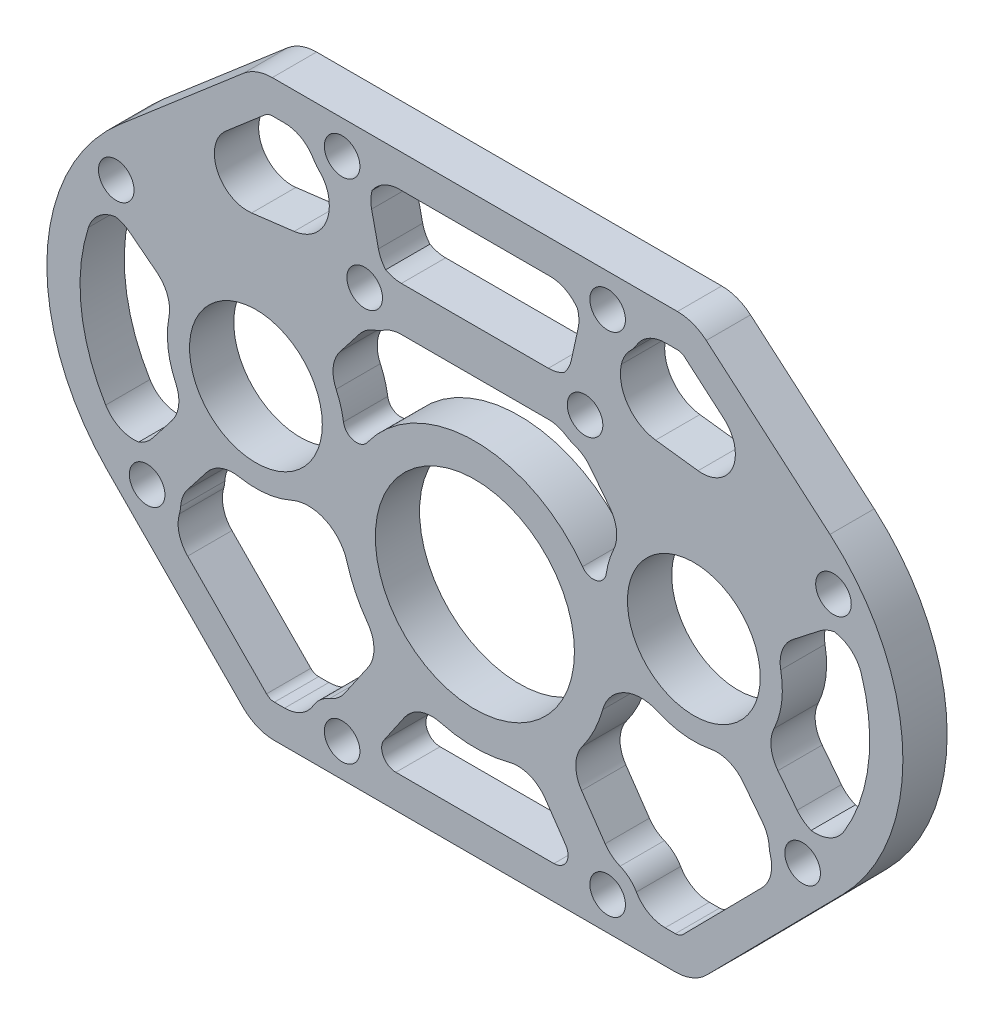
SolidWorks part; units mm, degrees
material "6061-T6 (SS)"
ref_plane "Front Plane" through (0, 0, 0) normal (0, 0, 1) x (1, 0, 0)
ref_plane "Top Plane" through (0, 0, 0) normal (0, 1, 0) x (1, 0, 0)
ref_plane "Right Plane" through (0, 0, 0) normal (1, 0, 0) x (0, 0, -1)
sketch "Sketch1" plane through (0, 0, 0) normal (0, 0, 1) x (1, 0, 0)
  line L0 (127, 25.4) -> (127, 0) construction
  line L1 (0, 0) -> (254, 0)
  line L2 (0, 0) -> (0, 25.4)
  line L3 (0, 25.4) -> (254, 25.4)
  line L4 (254, 0) -> (254, 25.4)
  line L18 (110.6338, 19.05) -> (106.9677, 12.7)
  line L19 (106.9677, 12.7) -> (110.6338, 6.35)
  line L20 (110.6338, 6.35) -> (117.9662, 6.35)
  line L21 (117.9662, 6.35) -> (121.6323, 12.7)
  line L22 (121.6323, 12.7) -> (117.9662, 19.05)
  line L23 (117.9662, 19.05) -> (110.6338, 19.05)
  circle A0 centre (82.8819, 22.86) radius 30 construction
  circle A1 centre (145.7181, 22.86) radius 30 construction
  circle A2 centre (82.8819, 22.86) radius 7.62 construction
  circle A3 centre (145.7181, 22.86) radius 8.636
  circle A4 centre (82.8819, 22.86) radius 8.636
  circle A5 centre (145.7181, 22.86) radius 7.62 construction
  circle A6 centre (114.3, 12.7) radius 25.4 construction
  circle A7 centre (114.3, 12.7) radius 26.67
  circle A8 centre (114.3, 12.7) radius 22.2377 construction
  circle A11 centre (114.3, 12.7) radius 6.35 construction
  dimension "D4" = 17.272
  dimension "D9" = 53.34
  dimension "D13" = 12.7
  dimension "D1" = 25.4
  dimension "D2" = 254
  dimension "D10" = 12.7
  dimension "D12" = 12.7
  dimension "D14" = 10.16
sketch "Sketch3" plane through (0, 0, 0) normal (0, 0, 1) x (1, 0, 0)
  line L0 (82.8819, 52.86) -> (145.7181, 52.86) construction
  line L5 (82.8819, -7.14) -> (145.7181, -7.14) construction
  line L6 (82.8819, 22.86) -> (98.4918, 42.8972) construction
  line L9 (114.3, 52.86) -> (114.3, -19.84) construction
  line L10 (63.3497, 45.6304) -> (82.8819, 62.385)
  line L25 (82.8819, 62.385) -> (145.7181, 62.385)
  line L26 (145.7181, 62.385) -> (165.2503, 45.6304)
  line L27 (110.6338, 19.05) -> (106.9677, 12.7)
  line L28 (106.9677, 12.7) -> (110.6338, 6.35)
  line L29 (110.6338, 6.35) -> (117.9662, 6.35)
  line L30 (117.9662, 6.35) -> (121.6323, 12.7)
  line L31 (121.6323, 12.7) -> (117.9662, 19.05)
  line L32 (117.9662, 19.05) -> (110.6338, 19.05)
  line L33 (110.565, 18.9308) -> (106.9677, 12.7)
  line L34 (106.9677, 12.7) -> (110.6338, 6.35)
  line L35 (110.6338, 6.35) -> (117.9662, 6.35)
  line L36 (117.9662, 6.35) -> (121.6323, 12.7)
  line L37 (121.6323, 12.7) -> (117.9662, 19.05)
  line L38 (117.9662, 19.05) -> (110.6338, 19.05)
  line L39 (96.3395, 30.6605) -> (132.2605, -5.2605) construction
  line L40 (82.8819, 22.86) -> (114.3, 12.7) construction
  line L41 (95.25, 57.6225) -> (133.35, 57.6225) construction
  line L43 (95.25, -15.0775) -> (133.35, -15.0775) construction
  line L44 (145.7181, -19.84) -> (167.0663, 1.7827)
  line L45 (82.8819, -19.84) -> (145.7181, -19.84)
  line L46 (61.5337, 1.7827) -> (82.8819, -19.84)
  line L47 (82.8819, 22.86) -> (67.272, 2.8228) construction
  line L48 (82.8819, 22.86) -> (67.272, 2.8228) construction
  line L49 (82.8819, 22.86) -> (62.8447, 38.4699) construction
  circle A2 centre (82.8819, 22.86) radius 30 construction
  circle A9 centre (114.3, 12.7) radius 26.67
  circle A10 centre (114.3, 12.7) radius 26.67 construction
  circle A11 centre (82.8819, 22.86) radius 8.636
  circle A12 centre (82.8819, 22.86) radius 8.636 construction
  circle A13 centre (145.7181, 22.86) radius 8.636
  circle A16 centre (145.7181, 22.86) radius 8.636 construction
  circle A17 centre (95.25, 57.6225) radius 2.5527
  circle A19 centre (114.3, 12.7) radius 25.4 construction
  circle A20 centre (114.3, 12.7) radius 22.2377 construction
  circle A22 centre (114.3, 12.7) radius 25.4 construction
  circle A23 centre (114.3, 12.7) radius 22.2377 construction
  arc A24 (112.6104, 26.8872) -> (104.6233, 2.1884) centre (82.8819, 22.86) ccw
  circle A25 centre (114.3, 12.7) radius 14.2875
  circle A26 centre (82.8819, 22.86) radius 9.525
  circle A27 centre (145.7181, 22.86) radius 9.525
  circle A37 centre (133.35, 57.6225) radius 2.5527
  circle A38 centre (133.35, -15.0775) radius 2.5527
  circle A39 centre (95.25, -15.0775) radius 2.5527
  circle A40 centre (67.272, 2.8228) radius 2.5527
  circle A41 centre (62.8447, 38.4699) radius 2.5527
  circle A42 centre (98.4918, 42.8972) radius 2.5527
  circle A43 centre (161.328, 2.8228) radius 2.5527
  circle A44 centre (165.7553, 38.4699) radius 2.5527
  circle A45 centre (130.1082, 42.8972) radius 2.5527
  circle A46 centre (95.25, -15.0775) radius 4.7625 construction
  arc A47 (123.9767, 2.1884) -> (115.9896, 26.8872) centre (145.7181, 22.86) ccw
  circle A48 centre (133.35, -15.0775) radius 4.7625 construction
  circle A49 centre (95.25, 57.6225) radius 4.7625 construction
  circle A50 centre (133.35, 57.6225) radius 4.7625 construction
  point P2 (114.3, 52.86)
  point P31 (114.3, -19.84)
  point P41 (114.3, 62.385)
  point P59 (114.3, 57.6225)
  point P60 (114.3, -15.0775)
  point P69 (114.3, 12.7)
  point P78 (82.8819, 22.86)
  point P84 (114.3, -22.0625)
  dimension "D3" = 70
  dimension "D4" = 9.525
  dimension "D2" = 45
  dimension "D8" = 25.4
  dimension "D14" = 28.575
  dimension "D15" = 19.05
  dimension "D16" = 3
  dimension "D5" = 5.1054
  dimension "D12" = 5.1054
  dimension "D7" = 4.7625
  dimension "D17" = 90
  dimension "2" = 50.8
  dimension "D6" = 19.05
  dimension "D18" = 7.9375
  dimension "D9" = 0
  dimension "D10" = 0
  dimension "D11" = 0
  dimension "D13" = 0
extrude "Boss-Extrude1" add sketch "Sketch3" along normal blind 6.35 contours A24 A10 L26 L25 L10 A37 A17 | A24 L46 L45 L44 A10 A38 A39 | A10 A24 A12 A40 A42 | A23 A24 A25 | A23 A22 A12 | A22 A24 A10 A12 | A22 A12 A10 A24 | A24 A22 A23 | A24 A10 A22 | A22 A24 A23 | A25 A24 A23 | A25 A23 A24 | A24 A23 A22 | A24 A22 A10 | A23 A24 A22 | A23 A45 A25 A44 | A22 A45 A23 A44 A16 | A23 A45 A22 | A22 A45 A16 A10 | A10 A16 A43 | A22 A44 A23 | A22 A44 A10 A16 | A10 A26 A12 | A22 A12 A10 | A12 A22 | A10 A27 A16 | A16 A22 | A22 A16 A10 region at (87.3231, 51.7029, 0) region at (114.3, 53.784, 0) region at (76.6658, -7.5892, 0) region at (98.4388, 17.8292, 0) region at (114.3, 34.3639, 0) region at (114.3, -6.358, 0) region at (141.2769, 51.7029, 0) region at (130.1612, 17.8292, 0)
fillet "Fillet1" radius 6.35 4 edges at (145.7181, -19.84, 3.175) (82.8819, -19.84, 3.175) (145.7181, 62.385, 3.175) (82.8819, 62.385, 3.175)
sketch "Sketch4" plane through (0, 0, 6.35) normal (0, 0, 1) x (1, 0, 0)
  line L0 (85.536, -15.0775) -> (143.064, -15.0775)
  line L1 (144.1937, -14.6053) -> (163.6773, 5.1287)
  line L2 (162.1496, 42.0156) -> (144.4013, 57.2399)
  line L3 (143.3677, 57.6225) -> (85.2323, 57.6225)
  line L4 (84.1987, 57.2399) -> (66.4504, 42.0156)
  line L5 (64.9227, 5.1287) -> (84.4063, -14.6053)
  line L6 (85.536, -19.84) -> (143.064, -19.84)
  line L7 (147.5827, -17.9514) -> (167.0663, 1.7827)
  line L8 (165.2503, 45.6304) -> (147.502, 60.8547)
  line L9 (143.3677, 62.385) -> (85.2323, 62.385)
  line L10 (81.098, 60.8547) -> (63.3497, 45.6304)
  line L11 (61.5337, 1.7827) -> (81.0173, -17.9514)
  line L12 (85.536, -19.84) -> (143.064, -19.84)
  line L13 (147.5827, -17.9514) -> (167.0663, 1.7827)
  line L14 (165.2503, 45.6304) -> (147.502, 60.8547)
  line L15 (143.3677, 62.385) -> (85.2323, 62.385)
  line L16 (81.098, 60.8547) -> (63.3497, 45.6304)
  line L17 (61.5337, 1.7827) -> (81.0173, -17.9514)
  line L18 (95.25, 57.6225) -> (98.4918, 42.8972) construction
  line L19 (98.4918, 42.8972) -> (130.1082, 42.8972) construction
  line L20 (130.1082, 42.8972) -> (133.35, 57.6225) construction
  line L21 (82.8819, 22.86) -> (114.3, 12.7) construction
  line L22 (114.3, 12.7) -> (95.25, -15.0775) construction
  line L23 (62.8447, 38.4699) -> (82.8819, 22.86) construction
  line L24 (82.8819, 22.86) -> (67.272, 2.8228) construction
  line L25 (165.7553, 38.4699) -> (145.7181, 22.86) construction
  line L26 (145.7181, 22.86) -> (161.328, 2.8228) construction
  line L27 (114.3, 12.7) -> (133.35, -15.0775) construction
  line L28 (114.3, 12.7) -> (145.7181, 22.86) construction
  line L29 (98.4918, 42.8972) -> (82.8819, 22.86) construction
  line L30 (130.1082, 42.8972) -> (145.7181, 22.86) construction
  line L31 (62.8447, 38.4699) -> (98.4918, 42.8972) construction
  line L32 (130.1082, 42.8972) -> (165.7553, 38.4699) construction
  line L33 (129.7168, 39.7464) -> (157.7573, 36.2639)
  line L34 (157.7573, 36.2639) -> (143.7668, 25.3647)
  line L35 (92.1493, 56.9399) -> (95.3911, 42.2146)
  line L36 (133.2089, 42.2146) -> (136.4507, 56.9399)
  line L37 (98.4918, 39.7222) -> (130.1082, 39.7222)
  line L38 (95.9872, 44.8485) -> (80.3773, 24.8112)
  line L39 (70.8427, 36.2639) -> (84.8332, 25.3647)
  line L40 (70.8427, 36.2639) -> (98.8832, 39.7464)
  line L41 (80.3773, 24.8112) -> (64.7674, 4.774)
  line L42 (81.905, 19.839) -> (113.3231, 9.679)
  line L43 (111.6816, 14.4957) -> (92.6316, -13.2818)
  line L44 (115.2769, 9.679) -> (146.695, 19.839)
  line L45 (111.6816, 10.9043) -> (130.7316, -16.8732)
  line L46 (143.2134, 20.9088) -> (158.8233, 0.8715)
  line L47 (127.6035, 40.946) -> (143.2134, 20.9088)
  line L48 (130.4995, 46.048) -> (169.4513, 41.2103)
  line L49 (171.2024, 38.6887) -> (147.6693, 20.3553)
  line L50 (98.3507, 58.3051) -> (101.5926, 43.5799)
  line L51 (127.0074, 43.5799) -> (130.2493, 58.3051)
  line L52 (98.4918, 46.0722) -> (130.1082, 46.0722)
  line L53 (100.9965, 40.946) -> (85.3866, 20.9088)
  line L54 (57.3976, 38.6887) -> (80.9307, 20.3553)
  line L55 (59.1487, 41.2103) -> (98.1005, 46.048)
  line L56 (85.3866, 20.9088) -> (69.7767, 0.8715)
  line L57 (83.8589, 25.881) -> (115.2769, 15.721)
  line L58 (116.9184, 10.9043) -> (97.8684, -16.8732)
  line L59 (113.3231, 15.721) -> (144.7411, 25.881)
  line L60 (116.9184, 14.4957) -> (135.9684, -13.2818)
  line L61 (148.2227, 24.8112) -> (163.8326, 4.774)
  line L62 (132.6128, 44.8485) -> (148.2227, 24.8112)
  line L63 (54.8467, 40.676) -> (98.1005, 46.048) construction
  line L64 (54.8467, 40.676) -> (80.9307, 20.3553) construction
  line L65 (130.4995, 46.048) -> (173.7533, 40.676) construction
  line L66 (173.7533, 40.676) -> (147.6693, 20.3553) construction
  arc A0 (143.064, -15.0775) -> (144.1937, -14.6053) centre (143.064, -13.49) ccw
  arc A1 (163.6773, 5.1287) -> (162.1496, 42.0156) centre (145.7181, 22.86) ccw
  arc A2 (144.4013, 57.2399) -> (143.3677, 57.6225) centre (143.3677, 56.035) ccw
  arc A3 (85.2323, 57.6225) -> (84.1987, 57.2399) centre (85.2323, 56.035) ccw
  arc A4 (66.4504, 42.0156) -> (64.9227, 5.1287) centre (82.8819, 22.86) ccw
  arc A5 (84.4063, -14.6053) -> (85.536, -15.0775) centre (85.536, -13.49) ccw
  arc A6 (143.064, -19.84) -> (147.5827, -17.9514) centre (143.064, -13.49) ccw
  arc A7 (167.0663, 1.7827) -> (165.2503, 45.6304) centre (145.7181, 22.86) ccw
  arc A8 (147.502, 60.8547) -> (143.3677, 62.385) centre (143.3677, 56.035) ccw
  arc A9 (85.2323, 62.385) -> (81.098, 60.8547) centre (85.2323, 56.035) ccw
  arc A10 (63.3497, 45.6304) -> (61.5337, 1.7827) centre (82.8819, 22.86) ccw
  arc A11 (81.0173, -17.9514) -> (85.536, -19.84) centre (85.536, -13.49) ccw
  arc A12 (143.064, -19.84) -> (147.5827, -17.9514) centre (143.064, -13.49) ccw
  arc A13 (167.0663, 1.7827) -> (165.2503, 45.6304) centre (145.7181, 22.86) ccw
  arc A14 (147.502, 60.8547) -> (143.3677, 62.385) centre (143.3677, 56.035) ccw
  arc A15 (85.2323, 62.385) -> (81.098, 60.8547) centre (85.2323, 56.035) ccw
  arc A16 (63.3497, 45.6304) -> (61.5337, 1.7827) centre (82.8819, 22.86) ccw
  arc A17 (81.0173, -17.9514) -> (85.536, -19.84) centre (85.536, -13.49) ccw
  circle A18 centre (95.25, 57.6225) radius 4.7625
  circle A19 centre (133.35, 57.6225) radius 4.7625
  circle A20 centre (95.25, -15.0775) radius 4.7625
  circle A21 centre (133.35, -15.0775) radius 4.7625
  circle A22 centre (161.328, 2.8228) radius 4.8142
  circle A23 centre (67.272, 2.8228) radius 4.8142
  circle A24 centre (62.8447, 38.4699) radius 4.6
  circle A25 centre (165.7553, 38.4699) radius 4.6
  circle A26 centre (98.4918, 42.8972) radius 4.7625
  circle A27 centre (130.1082, 42.8972) radius 4.7625
  circle A28 centre (114.3, 12.7) radius 19.05
  circle A29 centre (82.8819, 22.86) radius 12.7
  circle A30 centre (145.7181, 22.86) radius 12.7
  dimension "D3" = 38.1
  dimension "D4" = 25.4
  dimension "D5" = 3.175
  dimension "D1" = 0
  dimension "D2" = 4.7625
  dimension "D6" = 3.175
extrude "Cut-Extrude1" cut sketch "Sketch4" against normal up to surface (6.35 mm away) contours A29 L54 A24 A4 A23 L41 | A26 L35 A18 L3 A3 L4 L55 | A27 L51 A19 L3 A18 L50 A26 L52 | A27 L48 L2 A2 L3 A19 L36 | A30 L61 A22 A1 A25 L49 | A30 L44 A28 L60 A21 L0 A0 L1 A22 L46 | A28 L58 A20 L0 A21 L45 | A29 L56 A23 L5 A5 L0 A20 L43 A28 L42 | A30 L47 A27 L37 A26 L53 A29 L57 A28 L59 region at (142.3086, -0.1956, 6.35) region at (114.3, -10.7853, 6.35) region at (86.2914, -0.1956, 6.35) region at (164.1431, 20.6053, 6.35) region at (114.3, 32.9152, 6.35) region at (64.4569, 20.6053, 6.35) region at (145.2048, 49.2972, 6.35) region at (114.3, 51.9634, 6.35) region at (83.3952, 49.2972, 6.35) up to face at (114.3, 22.1956, 0)
fillet "Fillet2" radius 4.7625 50 edges at (66.5888, 42.1343, 3.175) (92.9125, 53.4731, 3.175) (90.4875, 57.6225, 3.175) (72.8202, 15.1108, 3.175) (66.9913, 7.6288, 3.175) (63.8856, 6.2446, 3.175) (60.4965, 34.5144, 3.175) (63.5193, 33.9196, 3.175) (71.2302, 27.9125, 3.175) (128.5875, -15.0775, 3.175) (100.0125, -15.0775, 3.175) (106.2948, -4.5864, 3.175) (122.3052, -4.5864, 3.175) (101.058, -0.995, 3.175) (94.6393, -10.3543, 3.175) (90.4875, -15.0775, 3.175) (70.6174, -0.6391, 3.175) (72.0006, 3.7263, 3.175) (77.8295, 11.2083, 3.175) (150.7705, 11.2083, 3.175) (157.9826, -0.6391, 3.175) (138.1125, -15.0775, 3.175) (133.9607, -10.3543, 3.175) (127.542, -0.995, 3.175) (156.5994, 3.7263, 3.175) (157.3698, 27.9125, 3.175) (165.0807, 33.9196, 3.175) (164.7144, 6.2446, 3.175) (161.6087, 7.6288, 3.175) (155.7798, 15.1108, 3.175) (168.1035, 34.5144, 3.175) (126.5584, 46.0722, 3.175) (102.0416, 46.0722, 3.175) (100.8294, 47.0466, 3.175) (99.114, 54.8384, 3.175) (100.0125, 57.6225, 3.175) (129.486, 54.8384, 3.175) (127.7706, 47.0466, 3.175) (128.5875, 57.6225, 3.175) (135.6875, 53.4731, 3.175) (138.1125, 57.6225, 3.175) (162.0112, 42.1343, 3.175) (135.6563, 30.6092, 3.175) (92.9437, 30.6092, 3.175) (102.0416, 39.7222, 3.175) (126.5584, 39.7222, 3.175) (129.785, 38.1457, 3.175) (98.815, 38.1457, 3.175) (95.559, 22.0974, 3.175) (133.041, 22.0974, 3.175)
sketch "Sketch6" plane through (0, 0, 0) normal (0, 0, -1) x (-1, 0, 0)
  line L0 (-125.6419, -15.0775) -> (-102.9581, -15.0775) construction
  line L1 (-94.5778, 45.6105) -> (-88.3626, 44.8386)
  line L2 (-95.4508, 15.4586) -> (-93.6052, 16.0554) construction
  line L3 (-134.9948, 16.0554) -> (-133.1492, 15.4586) construction
  line L4 (-95.4508, 15.4586) -> (-93.6052, 16.0554)
  line L5 (-134.9948, 16.0554) -> (-133.1492, 15.4586)
  line L10 (-128.7239, -13.9458) -> (-124.3792, -7.6106) construction
  line L12 (-135.3187, 51.7979) -> (-133.9721, 45.6813) construction
  line L13 (-146.3291, 44.082) -> (-134.0222, 45.6105) construction
  line L14 (-94.5778, 45.6105) -> (-82.2709, 44.082) construction
  line L15 (-94.6279, 45.6813) -> (-93.2813, 51.7979) construction
  line L16 (-99.8761, -13.9458) -> (-104.2208, -7.6106) construction
  line L17 (-128.7239, -13.9458) -> (-127.318, -11.8957)
  line L18 (-135.3187, 51.7979) -> (-133.9721, 45.6813)
  line L19 (-140.2374, 44.8386) -> (-134.0222, 45.6105)
  line L21 (-94.6279, 45.6813) -> (-93.2813, 51.7979)
  line L22 (-99.8761, -13.9458) -> (-101.282, -11.8957)
  arc A0 (-135.3187, 51.7979) -> (-140.2374, 44.8386) centre (-140.9478, 50.5586) cw
  arc A1 (-97.4046, 21.5005) -> (-95.4485, 24.6959) centre (-100.161, 25.3843) ccw
  arc A2 (-93.2813, 51.7979) -> (-88.3626, 44.8386) centre (-87.6522, 50.5586) ccw
  arc A3 (-127.318, -11.8957) -> (-125.6419, -15.0775) centre (-125.6419, -13.0451) ccw
  arc A4 (-97.4046, 21.5005) -> (-98.8607, 23.8594) centre (-114.3, 12.7) ccw
  arc A5 (-101.282, -11.8957) -> (-102.9581, -15.0775) centre (-102.9581, -13.0451) cw
  arc A6 (-135.3187, 51.7979) -> (-136.6599, 54.1982) centre (-139.9698, 50.7739) ccw construction
  arc A7 (-94.5778, 45.6105) -> (-94.6279, 45.6813) centre (-98.4918, 42.8972) ccw construction
  arc A8 (-102.9581, -15.0775) -> (-99.8761, -13.9458) centre (-102.9581, -10.315) ccw construction
  arc A9 (-128.7239, -13.9458) -> (-125.6419, -15.0775) centre (-125.6419, -10.315) ccw construction
  arc A10 (-102.9581, -15.0775) -> (-99.8761, -13.9458) centre (-102.9581, -10.315) ccw
  arc A11 (-128.7239, -13.9458) -> (-125.6419, -15.0775) centre (-125.6419, -10.315) ccw
  arc A12 (-133.9721, 45.6813) -> (-134.0222, 45.6105) centre (-130.1082, 42.8972) ccw construction
  arc A13 (-94.5778, 45.6105) -> (-94.6279, 45.6813) centre (-98.4918, 42.8972) ccw
  arc A14 (-133.9721, 45.6813) -> (-134.0222, 45.6105) centre (-130.1082, 42.8972) ccw
  arc A15 (-140.5415, 11.2629) -> (-132.6423, 7.5559) centre (-138.1921, 5.9995) cw
  arc A16 (-148.1162, 10.3885) -> (-134.9948, 16.0554) centre (-145.7181, 22.86) ccw construction
  arc A17 (-133.1492, 15.4586) -> (-129.6949, 1.4795) centre (-114.3, 12.7) ccw construction
  arc A18 (-95.9577, 7.5559) -> (-88.0585, 11.2629) centre (-90.4079, 5.9995) cw
  arc A19 (-98.9051, 1.4795) -> (-95.4508, 15.4586) centre (-114.3, 12.7) ccw construction
  arc A20 (-93.6052, 16.0554) -> (-80.4838, 10.3885) centre (-82.8819, 22.86) ccw construction
  arc A21 (-93.6052, 16.0554) -> (-88.0585, 11.2629) centre (-82.8819, 22.86) ccw
  arc A22 (-95.9577, 7.5559) -> (-95.4508, 15.4586) centre (-114.3, 12.7) ccw
  arc A23 (-133.1492, 15.4586) -> (-132.6423, 7.5559) centre (-114.3, 12.7) ccw
  arc A24 (-140.5415, 11.2629) -> (-134.9948, 16.0554) centre (-145.7181, 22.86) ccw
  arc A25 (-133.1515, 24.6959) -> (-129.7393, 23.8594) centre (-131.2757, 24.9699) ccw
  arc A26 (-133.1515, 24.6959) -> (-131.1954, 21.5005) centre (-128.439, 25.3843) ccw construction
  arc A27 (-97.4046, 21.5005) -> (-131.1954, 21.5005) centre (-114.3, 12.7) ccw construction
  arc A28 (-95.4485, 24.6959) -> (-98.8607, 23.8594) centre (-97.3243, 24.9699) cw
  arc A29 (-97.4046, 21.5005) -> (-95.4485, 24.6959) centre (-100.161, 25.3843) ccw construction
  arc A30 (-133.1515, 24.6959) -> (-131.1954, 21.5005) centre (-128.439, 25.3843) ccw
  arc A31 (-129.7393, 23.8594) -> (-131.1954, 21.5005) centre (-114.3, 12.7) ccw
extrude "Boss-Extrude2" add sketch "Sketch6" against normal up to surface (6.35 mm away) up to face at (114.3, 22.1956, 6.35)
equation "\"NEO\"= 60mm"
equation "\"D3@Sketch1\"=\"NEO\""
equation "\"D5@Sketch1\"=\"NEO\""
